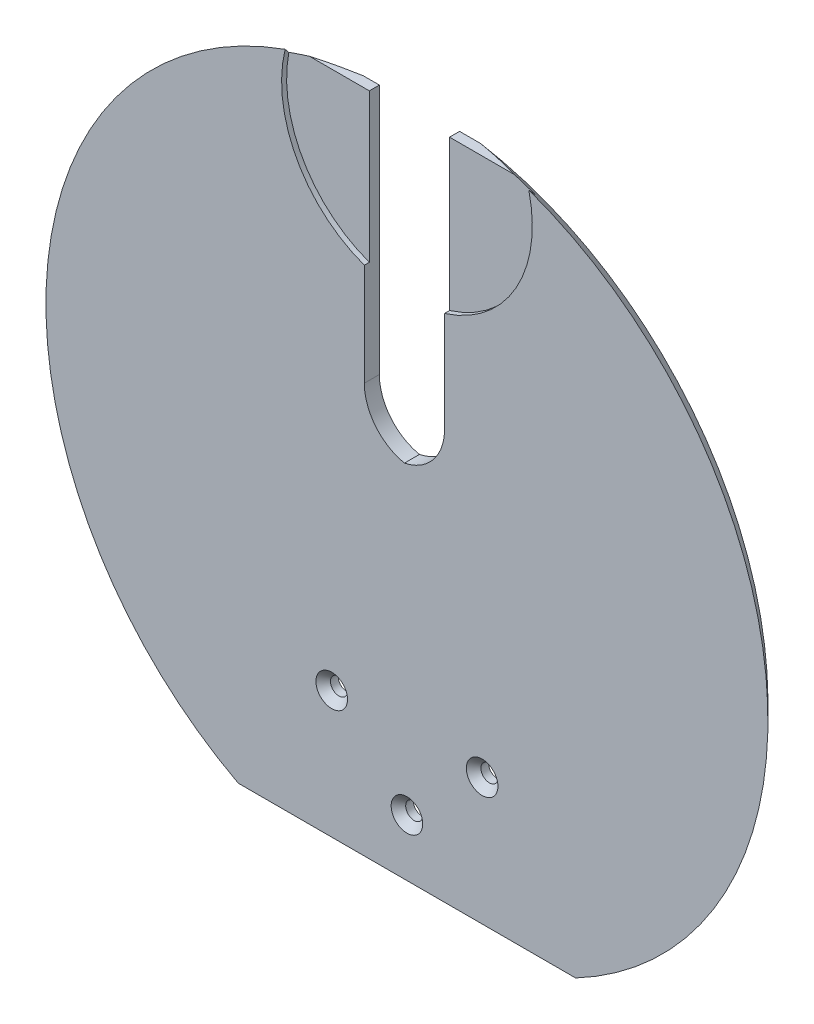
SolidWorks part; units mm, degrees
material "PET"
ref_plane "Front Plane" through (0, 0, 0) normal (0, 0, 1) x (1, 0, 0)
ref_plane "Top Plane" through (0, 0, 0) normal (0, 1, 0) x (1, 0, 0)
ref_plane "Right Plane" through (0, 0, 0) normal (1, 0, 0) x (0, 0, -1)
sketch "Sketch1" plane through (0, 0, 0) normal (0, 0, 1) x (1, 0, 0)
  line L0 (-9.944, -71.31) -> (9.944, -71.31) construction
  line L1 (-66.4124, -27.81) -> (66.4124, -27.81) construction
  line L2 (-35.1981, -62.81) -> (35.1981, -62.81) construction
  line L3 (0, -27.81) -> (0, -62.81) construction
  line L4 (-23.6643, 68) -> (23.6643, 68)
  line L5 (-31.3634, -64.81) -> (31.3634, -64.81)
  arc A0 (-23.6643, 68) -> (23.6643, 68) centre (0, 0) ccw
  circle A1 centre (0, -52.31) radius 2.397 construction
  circle A2 centre (-15, -38.31) radius 2.5305 construction
  circle A3 centre (15, -38.31) radius 2.5603 construction
  arc A4 (23.6643, 68) -> (-23.6643, 68) centre (0, 0) ccw construction
  point P13 (0, -45.31)
  dimension "D1" = 144
  dimension "D2" = 71.31
  dimension "D3" = 43.5
  dimension "D4" = 35
  dimension "D5" = 7
  dimension "D6" = 15
  dimension "D7" = 15
  dimension "D8" = 7
  dimension "D9" = 68
  dimension "D10" = 2
extrude "Boss-Extrude2" add sketch "Sketch1" along normal blind 3 contours A0 L4
sketch "Sketch2" plane through (0, 0, 3) normal (0, 0, 1) x (1, 0, 0)
  point P0 (15, -38.31)
  point P3 (-15, -38.31)
  point P6 (0, -52.31)
hole_wizard "CSK for M3 Countersunk Flat Head Screw1" positions "Sketch2" profile "Sketch3" countersink size "M3" standard "ISO"
sketch "Sketch3" plane through (15, -38.31, 3) normal (1, 0, 0) x (0, -1, 0)
  line L0 (0, 0) -> (0, 4.0215)
  line L1 (0, 4.0215) -> (1.7, 3)
  line L2 (1.7, 3) -> (1.7, 1.45)
  line L3 (1.7, 1.45) -> (3.15, 0)
  line L5 (3.15, 0) -> (0, 0)
  line L6 (-1.7, 1.45) -> (-3.15, 0) construction
  line L10 (0, 4.0215) -> (-1.7, 3) construction
  line L11 (0, -6.35) -> (0, 107.95) construction
  dimension "Hole Dia." = 3.4
  dimension "Hole Depth" = 3
  dimension "Near C'Sink Dia." = 6.3
  dimension "Near C'Sink Angle" = 90
  dimension "Drill Angle" = 118
sketch "Sketch4" plane through (0, 0, 3) normal (0, 0, 1) x (1, 0, 0)
  line L5 (23.6643, 68) -> (-23.6643, 68)
  line L6 (23.6643, 68) -> (-23.6643, 68)
  line L7 (-8.5, 8) -> (7.5, 8)
  line L8 (-8.5, 8) -> (-8.5, 68)
  line L9 (-8.5, 68) -> (7.5, 68)
  line L10 (7.5, 8) -> (7.5, 68)
  arc A1 (-23.6643, 68) -> (23.6643, 68) centre (0, 0) ccw
  arc A2 (-23.6643, 68) -> (23.6643, 68) centre (0, 0) ccw
  dimension "D1" = 60
  dimension "D3" = 16
  dimension "D4" = 0
extrude "Cut-Extrude1" cut sketch "Sketch4" against normal up to surface (3 mm away) contours L7 L10 L6 L8 region at (-0.5, 38, 3) up to face at (-13.3, -38.31, 0)
sketch "Sketch5" plane through (0, 0, 3) normal (0, 0, 1) x (1, 0, 0)
  circle A0 centre (0, 61.9) radius 25
  dimension "D1" = 50
  dimension "D2" = 61.9
extrude "Cut-Extrude2" cut sketch "Sketch5" against normal blind 1
fillet "Fillet1" radius 10 2 edges at (-8.5, 8, 1.5) (7.5, 8, 1.5)
extrude "Cut-Extrude3" cut sketch "Sketch1<3>" along normal blind 21 contours L5 A0 region at (0, -67.6987, 0)
sketch "Sketch1<3>" plane through (0, 0, 0) normal (0, 0, 1) x (1, 0, 0) same geometry as "Sketch1"
chamfer "Chamfer2" distance 5 angle 30 1 edges at (0, -64.81, 0) first distance on face at (0, -64.81, 1.5)
chamfer "Chamfer3" distance 3 angle 45 2 edges at (-71.6383, 7.2074, 0) (71.6383, 7.2074, 0)
